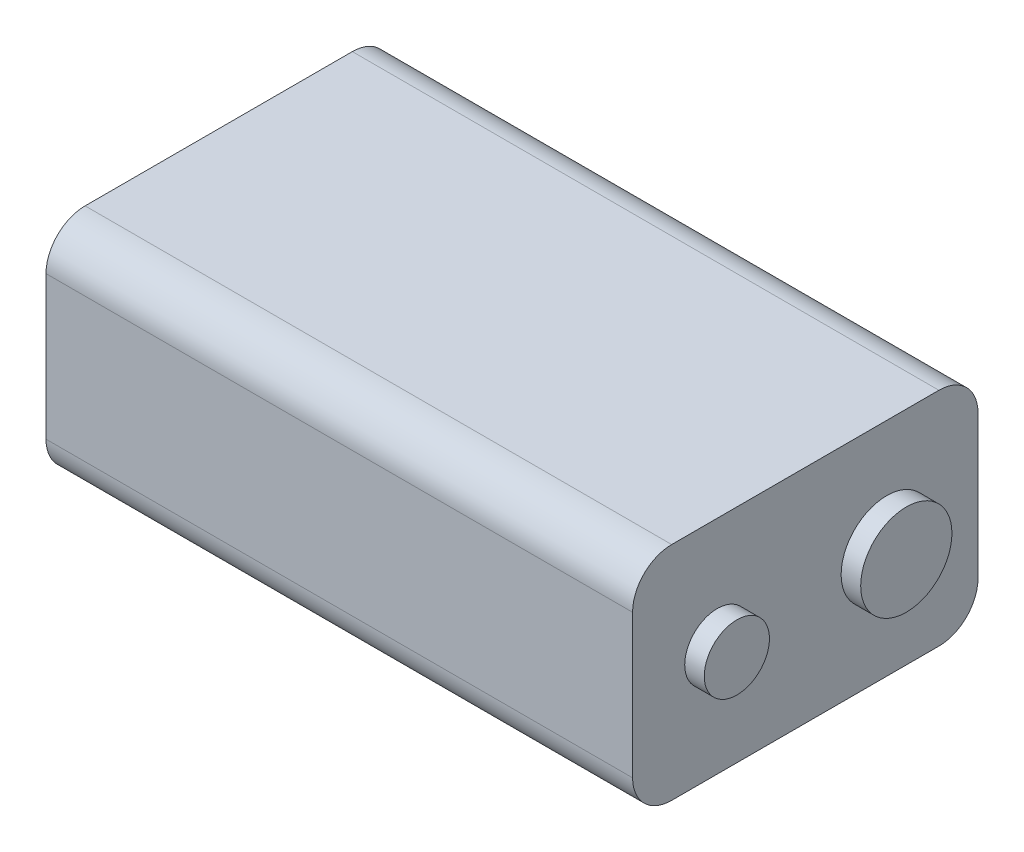
SolidWorks part; units mm, degrees
ref_plane "Front Plane" through (0, 0, 0) normal (0, 0, 1) x (1, 0, 0)
ref_plane "Top Plane" through (0, 0, 0) normal (0, 1, 0) x (1, 0, 0)
ref_plane "Right Plane" through (0, 0, 0) normal (1, 0, 0) x (0, 0, -1)
sketch "Sketch1" plane through (0, 0, 0) normal (0, 1, 0) x (1, 0, 0)
  line L1 (-21.9474, 18.298) -> (23.0526, 18.298)
  line L2 (-21.9474, 18.298) -> (-21.9474, -8.202)
  line L3 (-21.9474, -8.202) -> (23.0526, -8.202)
  line L4 (23.0526, 18.298) -> (23.0526, -8.202)
  dimension "D1" = 45
  dimension "D2" = 26.5
extrude "Boss-Extrude1" add sketch "Sketch1" along normal blind 17
fillet "Fillet1" radius 3 4 edges at (0.5526, 17, -18.298) (0.5526, 0, -18.298) (0.5526, 0, 8.202) (0.5526, 17, 8.202)
sketch "Sketch2" plane through (23.0526, 0, 0) normal (1, 0, 0) x (0, 0, -1)
  line L0 (18.298, 14) -> (18.298, 3) construction
  line L4 (-8.202, 14) -> (-8.202, 3) construction
  circle A0 centre (11.298, 8.5) radius 3.5
  circle A1 centre (-1.702, 8.5) radius 2.5
  point P4 (0, 0)
  point P7 (18.298, 8.5)
  dimension "D3" = 5
  dimension "D4" = 7
  dimension "D1" = 13
  dimension "D2" = 6.5
extrude "Boss-Extrude2" add sketch "Sketch2" along normal blind 1.5
